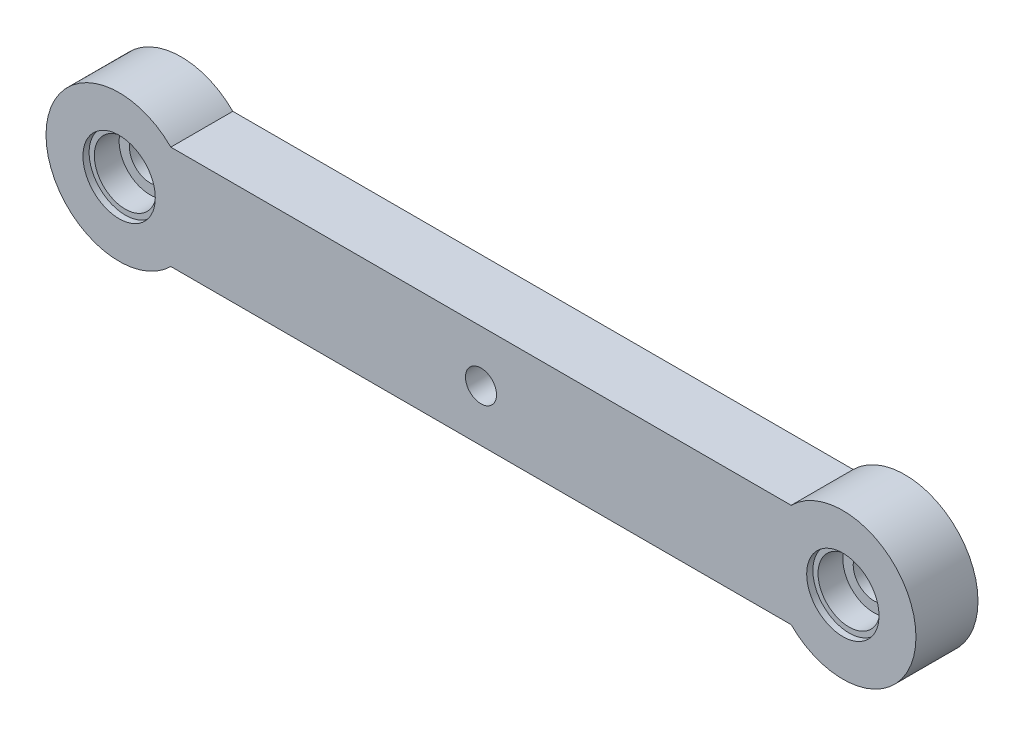
SolidWorks part; units mm, degrees
ref_plane "Front Plane" through (0, 0, 0) normal (0, 0, 1) x (1, 0, 0)
ref_plane "Top Plane" through (0, 0, 0) normal (0, 1, 0) x (1, 0, 0)
ref_plane "Right Plane" through (0, 0, 0) normal (1, 0, 0) x (0, 0, -1)
sketch "Sketch1" plane through (0, 0, 0) normal (0, 0, 1) x (1, 0, 0)
  line L0 (-40, 5) -> (-30, -5)
  line L1 (-40, 5) -> (40, 5)
  line L2 (-40, 5) -> (-40, -5)
  line L3 (-40, -5) -> (40, -5)
  line L4 (40, 5) -> (40, -5)
  line L5 (-40, 5) -> (40, -5) construction
  line L6 (-40, -5) -> (40, 5) construction
  line L7 (0, 5) -> (0, -5) construction
  circle A0 centre (-35, 0) radius 7.0711
  circle A1 centre (-35, 0) radius 3
  circle A2 centre (35, 0) radius 7.0711
  circle A3 centre (35, 0) radius 3
  point P0 (0, 0)
  dimension "D3" = 6
  dimension "D1" = 80
  dimension "D2" = 10
extrude "Boss-Extrude1" add sketch "Sketch1" along normal blind 6 contours L2 L1 L4 L3 | A0 | A2 | A3 | A1
sketch "Sketch2" plane through (0, 0, 6) normal (0, 0, 1) x (1, 0, 0)
  line L0 (-35, 7.0711) -> (-35, -7.0711)
  line L1 (0, 5) -> (0, -5)
  line L2 (-30, 5) -> (30, 5) construction
  line L3 (-30, -5) -> (30, -5) construction
  arc A0 (-30, 5) -> (-30, -5) centre (-35, 0) ccw construction
  circle A1 centre (-35, 0) radius 3
  circle A2 centre (35, 0) radius 3
  dimension "D1" = 6
extrude "Cut-Extrude1" cut sketch "Sketch2" against normal blind 3 contours A2 | A1
sketch "Sketch3" plane through (0, 0, 6) normal (0, 0, 1) x (1, 0, 0)
  line L0 (-35, 7.0711) -> (-35, -7.0711)
  line L1 (0, 5) -> (0, -5)
  line L2 (-30, 5) -> (30, 5) construction
  line L3 (-30, -5) -> (30, -5) construction
  arc A0 (-30, 5) -> (-30, -5) centre (-35, 0) ccw construction
  circle A1 centre (-35, 0) radius 2
  circle A2 centre (35, 0) radius 2
  dimension "D1" = 4
extrude "Cut-Extrude2" cut sketch "Sketch3" against normal through all contours A1 | A2
sketch "Sketch4" plane through (0, 0, 6) normal (0, 0, 1) x (1, 0, 0)
  line L0 (0, 5) -> (0, -5)
  line L1 (-30, 5) -> (30, 5) construction
  line L2 (-30, -5) -> (30, -5) construction
  line L3 (-35, 7.0711) -> (-35, -7.0711)
  arc A0 (-30, 5) -> (-30, -5) centre (-35, 0) ccw construction
  circle A1 centre (-35, 0) radius 3.5
  circle A2 centre (35, 0) radius 3.5
  dimension "D1" = 7
extrude "Cut-Extrude3" cut sketch "Sketch4" against normal blind 0.6 contours A1 | A2
sketch "Sketch5" plane through (0, 0, 6) normal (0, 0, 1) x (1, 0, 0)
  line L0 (0, 5) -> (0, -5)
  line L1 (-30, 5) -> (30, 5) construction
  line L2 (-30, -5) -> (30, -5) construction
  circle A0 centre (0, 0) radius 1.5
  dimension "D1" = 3
extrude "Cut-Extrude4" cut sketch "Sketch5" against normal through all and the other way blind 24 contours A0
